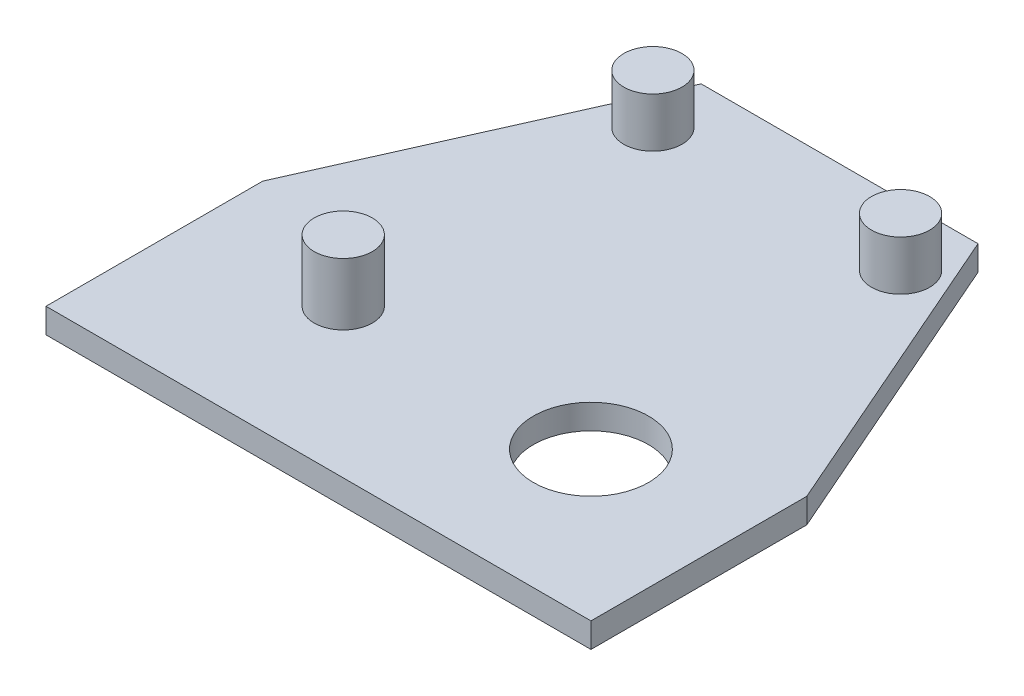
SolidWorks part; units mm, degrees
ref_plane "Front Plane" through (0, 0, 0) normal (0, 0, 1) x (1, 0, 0)
ref_plane "Top Plane" through (0, 0, 0) normal (0, 1, 0) x (1, 0, 0)
ref_plane "Right Plane" through (0, 0, 0) normal (1, 0, 0) x (0, 0, -1)
sketch "Sketch1" plane through (0, 0, 0) normal (0, 1, 0) x (1, 0, 0)
  line L1 (-20, 10) -> (20, 10)
  line L2 (-20, 10) -> (-20, -10)
  line L3 (-20, -10) -> (20, -10)
  line L4 (20, 10) -> (20, -10)
  point P4 (0, 10)
  point P6 (20, 0)
  dimension "D1" = 40
  dimension "D2" = 20
extrude "Boss-Extrude1" add sketch "Sketch1" along normal blind 2
sketch "Sketch2" plane through (0, 2, 0) normal (0, 1, 0) x (1, 0, 0)
  line L0 (-20, 0) -> (-4, 0) construction
  line L1 (-20, 10) -> (-20, -10) construction
  circle A0 centre (-4, 0) radius 2.35
  dimension "D2" = 4.7
  dimension "D1" = 16
sketch "Sketch5" plane through (0, 2, 0) normal (0, 1, 0) x (1, 0, 0)
  line L1 (-20, 10) -> (30, 10)
  line L2 (-20, 10) -> (-20, 30)
  line L3 (-20, 30) -> (30, 30)
  line L4 (30, 10) -> (30, 30)
  dimension "D1" = 20
extrude "Boss-Extrude4" add sketch "Sketch5" against normal blind 2
sketch "Sketch6" plane through (0, 2, 0) normal (0, 1, 0) x (1, 0, 0)
  line L0 (-20, 25) -> (20, 25) construction
  line L1 (-20, 30) -> (-20, -10) construction
  line L2 (20, -10) -> (20, 10) construction
  line L3 (30, 30) -> (-20, 30) construction
  line L4 (0, 30) -> (0, 25) construction
  circle A0 centre (-10, 25) radius 2.35
  circle A1 centre (10, 25) radius 2.35
  dimension "D2" = 4.7
  dimension "D3" = 4.7
  dimension "D4" = 20
  dimension "D1" = 5
  dimension "D5" = 10
extrude "Boss-Extrude5" add sketch "Sketch6" along normal blind 4
sketch "Sketch7" plane through (0, 0, 0) normal (0, -1, 0) x (1, 0, 0)
  line L1 (-11.55, -6.3) -> (-7, -6.3)
  line L2 (-11.55, -6.3) -> (-11.55, 6.3)
  line L3 (-11.55, 6.3) -> (-7, 6.3)
  line L4 (-7, -6.3) -> (-7, 6.3)
  line L5 (16, 6.3) -> (20.55, 6.3)
  line L6 (16, 6.3) -> (16, -6.2998)
  line L7 (16, -6.2998) -> (20.55, -6.2998)
  line L8 (20.55, 6.3) -> (20.55, -6.2998)
sketch "Sketch15" plane through (0, 2, 0) normal (0, 1, 0) x (1, 0, 0)
  line L0 (-20, 0) -> (17.0642, 0) construction
  line L1 (-20, 30) -> (-20, -10) construction
  line L2 (-20, -10) -> (20, -10) construction
  line L4 (0, -10) -> (0, 30) construction
  line L5 (30, 30) -> (-20, 30) construction
  circle A0 centre (10, 0) radius 4.65
  dimension "D2" = 9.3
  dimension "D1" = 10
extrude "Cut-Extrude6" cut sketch "Sketch15" against normal blind 6
sketch "Sketch17" plane through (0, 2, 0) normal (0, 1, 0) x (1, 0, 0)
  line L1 (20, 10) -> (30, 10)
  line L2 (20, 10) -> (20, 30)
  line L3 (20, 30) -> (30, 30)
  line L4 (30, 10) -> (30, 30)
extrude "Cut-Extrude8" cut sketch "Sketch17" against normal through all
sketch "Sketch18" plane through (0, 2, 0) normal (0, 1, 0) x (1, 0, 0)
  line L0 (20, 10) -> (-20, 10) construction
  line L1 (20, -10) -> (20, 30) construction
  line L2 (-20, 30) -> (-20, -10) construction
  line L3 (11.25, 30) -> (-11.1, 30) construction
  line L4 (20, 30) -> (-20, 30) construction
  line L5 (-11.1, 30) -> (-20, 10) construction
  line L6 (11.25, 30) -> (20, 10) construction
  line L7 (-11.1, 30) -> (-20, 10)
  line L8 (-20, 10) -> (-20, 30)
  line L9 (-20, 30) -> (-11.1, 30)
  line L10 (20, 10) -> (11.25, 30)
  line L11 (11.25, 30) -> (20, 30)
  line L12 (20, 30) -> (20, 10)
extrude "Cut-Extrude9" cut sketch "Sketch18" against normal blind 2
sketch "Sketch19" plane through (0, 2, 0) normal (0, 1, 0) x (1, 0, 0)
  circle A0 centre (-10, 0) radius 2.35
  dimension "D2" = 4.7
extrude "Boss-Extrude6" add sketch "Sketch19" along normal blind 5
sketch "Sketch20" plane through (0, 2, 0) normal (0, 1, 0) x (1, 0, 0)
  line L0 (-20, 10) -> (-22, 5.5056)
  line L1 (20, -10) -> (-20, -10)
  line L3 (20, -12) -> (-20, -12)
  line L6 (-20, 10) -> (-20, -10)
  line L7 (-20, -12) -> (-22, -12)
  line L8 (-22, 5.5056) -> (-22, -12)
  line L10 (20, 10) -> (20, -10)
  line L11 (20, -12) -> (22, -12)
  line L12 (22, 5.4286) -> (22, -12)
  line L13 (20, 10) -> (22, 5.4286)
  line L14 (-20, 10) -> (-11.1, 30) construction
  point P9 (0, 0)
  point P12 (0, 0)
  point P16 (-21.9687, 11.9933)
  dimension "D1" = 2
  dimension "D3" = 2
  dimension "D4" = 180
  dimension "D5" = 2
extrude "Boss-Extrude7" add sketch "Sketch20" against normal blind 2
